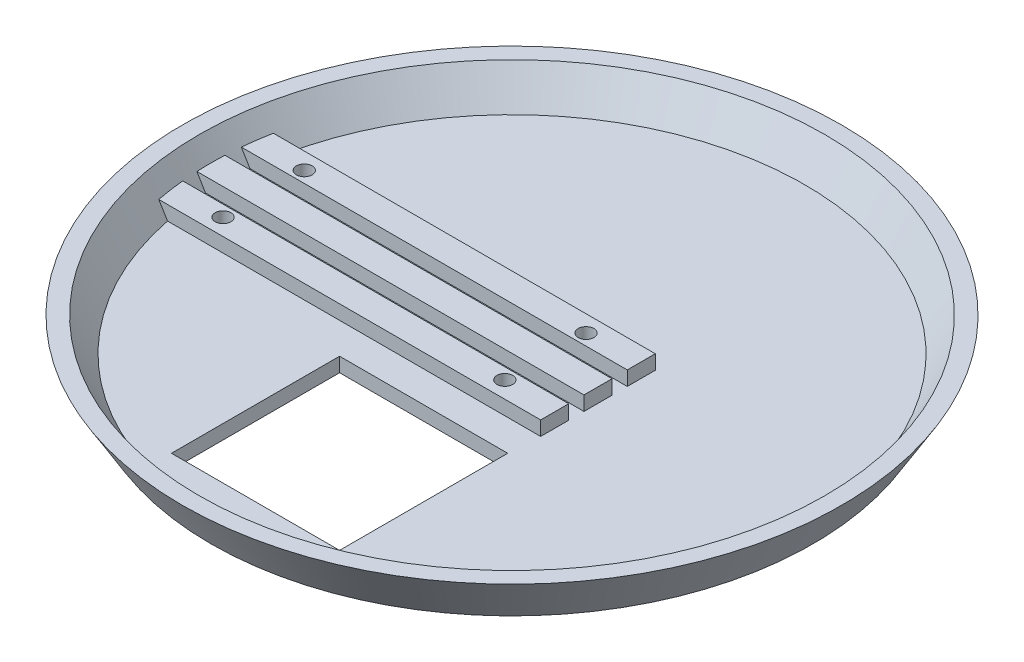
SolidWorks part; units mm, degrees
ref_plane "Front Plane" through (0, 0, 0) normal (0, 0, 1) x (1, 0, 0)
ref_plane "Top Plane" through (0, 0, 0) normal (0, 1, 0) x (1, 0, 0)
ref_plane "Right Plane" through (0, 0, 0) normal (1, 0, 0) x (0, 0, -1)
sketch "Sketch1" plane through (0, 0, 0) normal (0, 0, 1) x (1, 0, 0)
  line L0 (0, 0) -> (63, 0)
  line L1 (63, 0) -> (69, 10)
  line L6 (0, 3) -> (61.3014, 3)
  line L7 (61.3014, 3) -> (65.5014, 10)
  line L8 (69, 10) -> (65.5014, 10)
  line L9 (0, 0) -> (0, 3)
  line L10 (61.3014, 3) -> (66.4275, 11.5435) construction
  dimension "D1" = 69
  dimension "D2" = 63
  dimension "D3" = 10
  dimension "D4" = 3
revolve "Revolve1" add sketch "Sketch1" angle 360 about L9
sketch "Sketch2" plane through (0, 3, 0) normal (0, 1, 0) x (1, 0, 0)
  line L0 (-17.6, -18.5) -> (-17.6, -53.7)
  line L1 (-17.6, -18.5) -> (17.6, -18.5)
  line L5 (17.6, -18.5) -> (17.6, -53.7)
  line L6 (-17.6, -53.7) -> (17.6, -53.7)
  point P1 (0, -18.5)
  dimension "D2" = 35.2
  dimension "D1" = 35.2
  dimension "D4" = 18.5
extrude "Cut-Extrude1" cut sketch "Sketch2" against normal through all
sketch "Sketch4" plane through (0, 0, 0) normal (1, 0, 0) x (0, 0, -1)
  line L0 (-6.1333, 3) -> (-12, 3)
  line L5 (-12, 3) -> (-12, 6)
  line L6 (-12, 6) -> (-6.1333, 6)
  line L7 (-6.1333, 6) -> (-6.1333, 3)
  line L8 (-2.9333, 3) -> (2.9333, 3)
  line L9 (2.9333, 3) -> (2.9333, 6)
  line L10 (2.9333, 6) -> (-2.9333, 6)
  line L11 (-2.9333, 6) -> (-2.9333, 3)
  line L12 (12, 3) -> (6.1333, 3)
  line L13 (6.1333, 3) -> (6.1333, 6)
  line L14 (6.1333, 6) -> (12, 6)
  line L15 (12, 6) -> (12, 3)
  point P13 (0, 3)
  dimension "D1" = 12
  dimension "D2" = 3
  dimension "D3" = 3
  dimension "D4" = 3.2
  dimension "D5" = 3.2
  dimension "D6" = 12
extrude "Boss-Extrude1" add sketch "Sketch4" along normal blind 10 and the other way blind 63.5
sketch "Sketch5" plane through (0, 0, 0) normal (0, 1, 0) x (1, 0, 0)
  line L0 (10, 2.9333) -> (10, -2.9333) construction
  circle A0 centre (7, -8.5) radius 1.65
  circle A1 centre (7, 0) radius 1.65
  circle A2 centre (7, 8.5) radius 1.65
  circle A6 centre (-52, 8.5) radius 1.65
  circle A8 centre (-52, -8.5) radius 1.65
  circle A9 centre (-22.5, 0) radius 1.65 [skipped]
  circle A10 centre (-52, 0) radius 1.65 [skipped]
  circle A11 centre (-22.5, 8.5) radius 1.65 [skipped]
  circle A12 centre (-22.5, -8.5) radius 1.65 [skipped]
  dimension "D2" = 3.3
  dimension "D3" = 8.5
  dimension "D6" = 3
  dimension "D7" = 59
  dimension "D4" = 8.5
  dimension "D5" = 3
extrude "Cut-Extrude2" cut sketch "Sketch5" along normal through all contours A2 | A0 | A8 | A6
sketch "Sketch7" [suppressed] plane through (10, 0, 0) normal (1, 0, 0) x (0, 0, -1)
  line L0 (-12, 37.9) -> (-6.1333, 37.9) construction
  line L1 (-12, 3) -> (-6.1333, 3)
  line L2 (-12, 3) -> (-12, 43)
  line L3 (-12, 43) -> (12, 43)
  line L4 (12, 3) -> (12, 43)
  line L5 (-2.9333, 37.9) -> (2.9333, 37.9) construction
  line L6 (-6.1333, 37.9) -> (-2.9333, 37.9)
  line L7 (-6.1333, 37.9) -> (-6.1333, 40.9)
  line L8 (-6.1333, 40.9) -> (-2.9333, 40.9)
  line L9 (-2.9333, 37.9) -> (-2.9333, 40.9)
  line L10 (12, 37.9) -> (6.1333, 37.9) construction
  line L11 (2.9333, 3) -> (2.9333, 6)
  line L12 (2.9333, 37.9) -> (6.1333, 37.9)
  line L13 (2.9333, 37.9) -> (2.9333, 40.9)
  line L14 (2.9333, 40.9) -> (6.1333, 40.9)
  line L15 (6.1333, 37.9) -> (6.1333, 40.9)
  line L20 (2.9333, 6) -> (6.1333, 6)
  line L21 (6.1333, 6) -> (6.1333, 3)
  line L22 (-6.1333, 3) -> (-6.1333, 6)
  line L23 (-6.1333, 6) -> (-2.9333, 6)
  line L24 (-2.9333, 6) -> (-2.9333, 3)
  line L25 (6.1333, 3) -> (12, 3)
  line L26 (-2.9333, 3) -> (2.9333, 3)
  circle A0 centre (0, 23.5) radius 8.5
  point P18 (0, 3)
  dimension "D6" = 17
  dimension "D7" = 20.5
  dimension "D1" = 24
  dimension "D2" = 40
  dimension "D3" = 3.2
  dimension "D4" = 3
  dimension "D5" = 37.9
sketch "Sketch8" plane through (10, 0, 0) normal (1, 0, 0) x (0, 0, -1)
  line L1 (-12, 6) -> (-6.1333, 6)
  line L2 (-12, 6) -> (-12, 3)
  line L3 (-12, 3) -> (-6.1333, 3)
  line L4 (-6.1333, 6) -> (-6.1333, 3)
  line L5 (-2.9333, 6) -> (2.9333, 6)
  line L6 (-2.9333, 6) -> (-2.9333, 3)
  line L7 (-2.9333, 3) -> (2.9333, 3)
  line L8 (2.9333, 6) -> (2.9333, 3)
  line L9 (6.1333, 6) -> (12, 6)
  line L10 (6.1333, 6) -> (6.1333, 3)
  line L11 (6.1333, 3) -> (12, 3)
  line L12 (12, 6) -> (12, 3)
  point P18 (0, 0)
  point P21 (-12, 6)
extrude "Boss-Extrude3" add sketch "Sketch8" along normal blind 8
